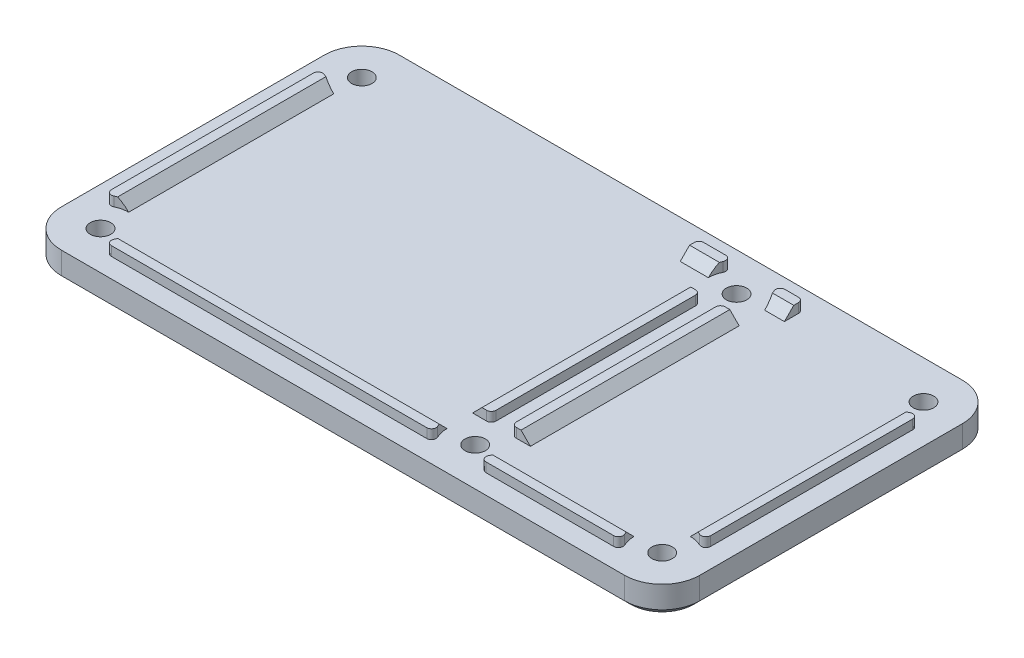
SolidWorks part; units mm, degrees
ref_plane "Plane XZ" through (0, 0, 0) normal (0, 0, 1) x (1, 0, 0)
ref_plane "Plane XY" through (0, 0, 0) normal (0, 1, 0) x (1, 0, 0)
ref_plane "Plane YZ" through (0, 0, 0) normal (1, 0, 0) x (0, 0, -1)
sketch "Sketch1" plane through (0, 0, 0) normal (0, 1, 0) x (1, 0, 0)
  line L0 (0, 28.575) -> (0, -28.575) construction
  line L1 (-47.625, 28.575) -> (47.625, 28.575)
  line L2 (-53.975, 22.225) -> (-53.975, -22.225)
  line L3 (-47.625, -28.575) -> (47.625, -28.575)
  line L4 (53.975, 22.225) -> (53.975, -22.225)
  arc A0 (47.625, -28.575) -> (53.975, -22.225) centre (47.625, -22.225) ccw
  arc A1 (47.625, 28.575) -> (53.975, 22.225) centre (47.625, 22.225) cw
  arc A2 (-47.625, 28.575) -> (-53.975, 22.225) centre (-47.625, 22.225) ccw
  arc A3 (-47.625, -28.575) -> (-53.975, -22.225) centre (-47.625, -22.225) cw
  point P11 (53.975, 28.575)
  point P14 (-53.975, 28.575)
  point P17 (-53.975, -28.575)
  dimension "D3" = 6.35
  dimension "D1" = 107.95
  dimension "D2" = 57.15
extrude "Boss-Extrude1" add sketch "Sketch1" along normal blind 4.7625
sketch "Sketch2" plane through (0, 4.7625, 0) normal (0, 1, 0) x (1, 0, 0)
  line L8 (50.8, -22.225) -> (50.8, 22.225)
  line L9 (47.625, 25.4) -> (-47.625, 25.4)
  line L10 (-50.8, 22.225) -> (-50.8, -22.225)
  line L11 (-47.625, -25.4) -> (47.625, -25.4)
  line L12 (50.8, -22.225) -> (50.8, 22.225) construction
  line L13 (47.625, 25.4) -> (-47.625, 25.4) construction
  line L14 (-50.8, 22.225) -> (-50.8, -22.225) construction
  line L15 (-47.625, -25.4) -> (47.625, -25.4) construction
  line L16 (-47.625, 25.4) -> (14.2875, 25.4) construction
  line L17 (14.2875, 25.4) -> (14.2875, -25.4) construction
  line L18 (14.2875, -25.4) -> (-47.625, -25.4) construction
  line L19 (47.625, -25.4) -> (17.4625, -25.4) construction
  line L20 (17.4625, -25.4) -> (17.4625, 25.4) construction
  line L21 (17.4625, 25.4) -> (47.625, 25.4) construction
  line L22 (-53.975, 22.225) -> (-53.975, -22.225) construction
  line L23 (-50.673, 22.225) -> (-50.673, -22.225)
  line L24 (14.1605, -25.273) -> (-47.625, -25.273)
  line L25 (14.1605, 25.273) -> (14.1605, -25.273)
  line L26 (-47.625, 25.273) -> (14.1605, 25.273)
  line L27 (47.625, -25.273) -> (17.5895, -25.273)
  line L28 (17.5895, -25.273) -> (17.5895, 25.273)
  line L29 (17.5895, 25.273) -> (47.625, 25.273)
  line L30 (50.673, -22.225) -> (50.673, 22.225)
  line L31 (12.573, -23.6855) -> (-47.625, -23.6855)
  line L32 (-49.0855, 22.225) -> (-49.0855, -22.225)
  line L33 (-47.625, 23.6855) -> (12.573, 23.6855)
  line L34 (12.573, 23.6855) -> (12.573, -23.6855)
  line L35 (19.177, -23.6855) -> (19.177, 23.6855)
  line L36 (19.177, 23.6855) -> (47.625, 23.6855)
  line L37 (49.0855, -22.225) -> (49.0855, 22.225)
  line L38 (47.625, -23.6855) -> (19.177, -23.6855)
  arc A8 (47.625, -25.4) -> (50.8, -22.225) centre (47.625, -22.225) ccw
  arc A9 (50.8, 22.225) -> (47.625, 25.4) centre (47.625, 22.225) ccw
  arc A10 (-47.625, 25.4) -> (-50.8, 22.225) centre (-47.625, 22.225) ccw
  arc A11 (-50.8, -22.225) -> (-47.625, -25.4) centre (-47.625, -22.225) ccw
  arc A12 (47.625, -25.4) -> (50.8, -22.225) centre (47.625, -22.225) ccw construction
  arc A13 (50.8, 22.225) -> (47.625, 25.4) centre (47.625, 22.225) ccw construction
  arc A14 (-47.625, 25.4) -> (-50.8, 22.225) centre (-47.625, 22.225) ccw construction
  arc A15 (-50.8, -22.225) -> (-47.625, -25.4) centre (-47.625, -22.225) ccw construction
  arc A16 (-47.625, 25.273) -> (-50.673, 22.225) centre (-47.625, 22.225) ccw
  arc A17 (-50.673, -22.225) -> (-47.625, -25.273) centre (-47.625, -22.225) ccw
  arc A18 (50.673, 22.225) -> (47.625, 25.273) centre (47.625, 22.225) ccw
  arc A19 (47.625, -25.273) -> (50.673, -22.225) centre (47.625, -22.225) ccw
  arc A20 (-49.0855, -22.225) -> (-47.625, -23.6855) centre (-47.625, -22.225) ccw
  arc A21 (-47.625, 23.6855) -> (-49.0855, 22.225) centre (-47.625, 22.225) ccw
  arc A22 (49.0855, 22.225) -> (47.625, 23.6855) centre (47.625, 22.225) ccw
  arc A23 (47.625, -23.6855) -> (49.0855, -22.225) centre (47.625, -22.225) ccw
  dimension "D2" = 68.2625
  dimension "D3" = 3.175
  dimension "D1" = 3.175
  dimension "D4" = 0.127
  dimension "D5" = 0.127
  dimension "D6" = 1.5875
  dimension "D7" = 1.5875
extrude "Boss-Extrude2" add sketch "Sketch2" along normal blind 1.5875
sketch "Sketch3" plane through (0, 4.7625, 0) normal (0, 1, 0) x (1, 0, 0)
  line L0 (12.573, 23.6855) -> (-47.625, 23.6855) construction
  line L1 (-44.45, 23.6855) -> (6.35, 23.6855)
  line L2 (-44.45, 23.6855) -> (-44.45, 25.273)
  line L3 (-44.45, 25.273) -> (6.35, 25.273)
  line L4 (6.35, 23.6855) -> (6.35, 25.273)
  line L5 (14.1605, 25.273) -> (-47.625, 25.273) construction
  line L6 (47.625, 25.273) -> (17.5895, 25.273) construction
  line L7 (44.2913, 25.273) -> (23.9712, 25.273)
  line L8 (44.2913, 25.273) -> (44.2913, 23.6855)
  line L9 (44.2913, 23.6855) -> (23.9712, 23.6855)
  line L10 (23.9712, 25.273) -> (23.9712, 23.6855)
  line L11 (47.625, 23.6855) -> (19.177, 23.6855) construction
  line L12 (-53.975, 22.225) -> (-53.975, -22.225) construction
  line L14 (17.5895, 0) -> (50.673, 0) construction
  line L15 (17.5895, 25.273) -> (17.5895, -25.273) construction
  line L16 (50.673, -22.225) -> (50.673, 22.225) construction
  line L17 (34.1313, 0) -> (34.1313, 23.6855) construction
  dimension "D1" = 50.8
  dimension "D2" = 20.32
  dimension "D3" = 9.525
extrude "Cut-Extrude1" cut sketch "Sketch3" along normal through all
hole_wizard "#4 Clearance Hole1" positions "Sketch4" profile "Sketch5" hole size "#4" standard "ANSI Inch" end condition through all
sketch "Sketch4" plane through (0, 0, 0) normal (0, -1, 0) x (-1, 0, 0)
  line L1 (47.498, -22.098) -> (-47.498, -22.098)
  line L2 (47.498, -22.098) -> (47.498, 22.098)
  line L3 (47.498, 22.098) -> (-47.498, 22.098)
  line L4 (-47.498, -22.098) -> (-47.498, 22.098)
  line L5 (-15.875, -22.098) -> (-15.875, 22.098)
  line L7 (47.625, -28.575) -> (-47.625, -28.575) construction
  line L8 (-47.625, 28.575) -> (47.625, 28.575) construction
  line L9 (53.975, 22.225) -> (53.975, -22.225) construction
  line L10 (-53.975, -22.225) -> (-53.975, 22.225) construction
  line L11 (-14.1605, 22.098) -> (-17.5895, 22.098)
  line L13 (-14.1605, -25.273) -> (-14.1605, 25.273) construction
  line L14 (-17.5895, 25.273) -> (-17.5895, -25.273) construction
  point P0 (47.498, 22.098)
  point P2 (47.498, -22.098)
  point P4 (-15.875, -22.098)
  point P6 (-15.875, 22.098)
  point P8 (-47.498, 22.098)
  point P10 (-47.498, -22.098)
  dimension "D1" = 6.477
  dimension "D2" = 6.477
  dimension "D3" = 6.477
  dimension "D4" = 6.477
sketch "Sketch5" plane through (-47.498, 0, -22.098) normal (1, 0, 0) x (0, 0, -1)
  line L0 (0, 0) -> (0, 6.35)
  line L1 (0, 6.35) -> (1.7272, 6.35)
  line L2 (1.7272, 6.35) -> (1.7272, 0)
  line L5 (1.7272, 0) -> (0, 0)
  line L11 (0, -6.35) -> (0, 107.95) construction
  dimension "Thru Hole Dia." = 3.4544
  dimension "Thru Hole Depth" = 6.35
sketch "Sketch6" plane through (0, 4.7625, 0) normal (0, 1, 0) x (1, 0, 0)
  circle A0 centre (47.498, 22.098) radius 4.7625
  circle A1 centre (47.498, -22.098) radius 4.7625
  circle A2 centre (15.875, -22.098) radius 4.7625
  circle A3 centre (15.875, 22.098) radius 4.7625
  circle A4 centre (-47.498, 22.098) radius 4.7625
  circle A5 centre (-47.498, -22.098) radius 4.7625
  dimension "D1" = 9.525
extrude "Cut-Extrude2" cut sketch "Sketch6" along normal through all
sketch "Sketch7" plane through (0, 4.7625, 0) normal (0, 1, 0) x (1, 0, 0)
  line L1 (19.9766, 17.6548) -> (11.8496, 17.6548)
  line L2 (19.9766, 17.6548) -> (19.9766, 20.0703)
  line L3 (19.9766, 20.0703) -> (11.8496, 20.0703)
  line L4 (11.8496, 17.6548) -> (11.8496, 20.0703)
  line L5 (20.2511, -21.0912) -> (10.8677, -21.0912)
  line L6 (20.2511, -21.0912) -> (20.2511, -17.6548)
  line L7 (20.2511, -17.6548) -> (10.8677, -17.6548)
  line L8 (10.8677, -21.0912) -> (10.8677, -17.6548)
extrude "Cut-Extrude3" cut sketch "Sketch7" along normal through all
chamfer "Chamfer1" distance 1.5875 angle 45 8 edges at (-49.0855, 4.7625, 0) (8.8674, 4.7625, -23.6855) (22.1682, 4.7625, -23.6855) (49.0855, 4.7625, 0) (31.6865, 4.7625, 23.6855) (-15.8115, 4.7625, 23.6855) (12.573, 4.7625, 0) (19.177, 4.7625, 0)
fillet "Fillet1" radius 0.7937 16 edges at (23.9712, 5.5563, -25.273) (19.4248, 5.5563, -25.273) (19.4248, 5.5563, 25.273) (50.673, 5.5563, 18.5482) (50.673, 5.5563, -18.5482) (12.3252, 5.5563, 25.273) (-43.9482, 5.5563, 25.273) (-50.673, 5.5563, 18.5482) (-50.673, 5.5563, -18.5482) (6.35, 5.5563, -25.273) (12.3252, 5.5563, -25.273) (43.9482, 5.5563, 25.273) (14.1605, 5.5563, 17.6548) (17.5895, 5.5563, 17.6548) (14.1605, 5.5563, -17.6548) (17.5895, 5.5563, -17.6548)
chamfer "Chamfer2" distance 1.016 angle 45 8 edges at (0, 0, 28.575) (52.1151, 0, 26.7151) (-52.1151, 0, 26.7151) (53.975, 0, 0) (-53.975, 0, 0) (52.1151, 0, -26.7151) (-52.1151, 0, -26.7151) (0, 0, -28.575)
